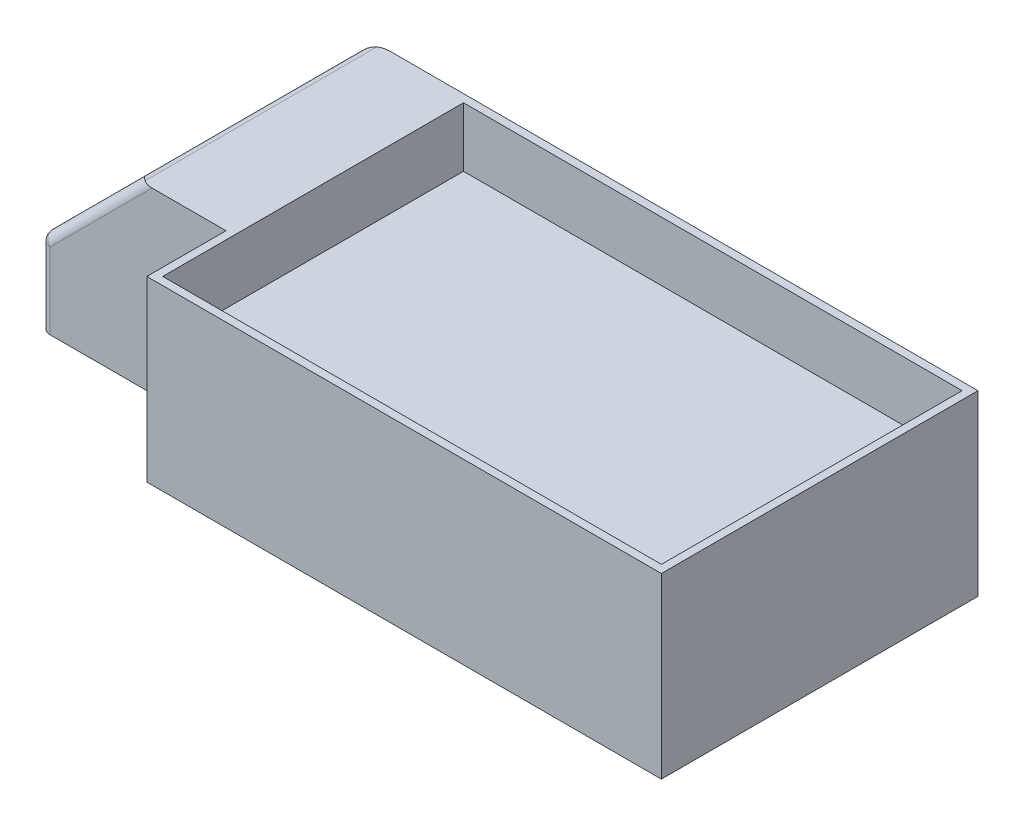
SolidWorks part; units mm, degrees
ref_plane "Front Plane" through (0, 0, 0) normal (0, 0, 1) x (1, 0, 0)
ref_plane "Top Plane" through (0, 0, 0) normal (0, 1, 0) x (1, 0, 0)
ref_plane "Right Plane" through (0, 0, 0) normal (1, 0, 0) x (0, 0, -1)
sketch "Sketch1" plane through (0, 0, 0) normal (0, 1, 0) x (1, 0, 0)
  line L1 (0, 0) -> (130, 0)
  line L2 (0, 0) -> (0, 80)
  line L3 (0, 80) -> (130, 80)
  line L4 (130, 0) -> (130, 80)
  dimension "D1" = 80
  dimension "D2" = 130
extrude "Boss-Extrude1" add sketch "Sketch1" along normal blind 45 contours L3 L4 L1 L2
sketch "Sketch3" plane through (0, 0, 0) normal (0, 0, 1) x (1, 0, 0)
  line L0 (0, 0) -> (0, 45)
  line L1 (-46.9514, 20.2513) -> (-46.9514, 0)
  line L2 (-46.9514, 0) -> (0, 0)
  line L3 (-46.9514, 20.2513) -> (-22.2027, 45)
  line L4 (-22.2027, 45) -> (0, 45)
  line L5 (0, 45) -> (0, 0) construction
  line L6 (0, 0) -> (130, 0) construction
  dimension "D1" = 35
extrude "Boss-Extrude3" add sketch "Sketch3" against normal up to surface (80 mm away) contours L3 L4 L0 L2 L1 up to face at (65, 22.5, -80)
extrude "Cut-Extrude1" cut sketch "Sketch3<4>" against normal blind 20
sketch "Sketch3<4>" plane through (0, 0, 0) normal (0, 0, 1) x (1, 0, 0) same geometry as "Sketch3"
fillet "Fillet2" radius 2.5 6 edges at (-46.9514, 20.2513, -50) (-34.5771, 32.6256, -80) (-22.2027, 45, -50) (-34.5771, 32.6256, -20) (-46.9514, 10.1256, -20) (-46.9514, 10.1256, -80)
shell "Shell2" thickness 4 removed face at (9.5198, 0, -37.5)
sketch "Sketch9" plane through (0, 45, 0) normal (0, 1, 0) x (1, 0, 0)
  line L0 (-18.6671, 80) -> (130, 80) construction
  line L1 (130, 0) -> (0, 0)
  line L2 (130, 0) -> (130, 80)
  line L3 (130, 80) -> (0, 80)
  line L4 (0, 0) -> (0, 80)
  line L5 (0, 0) -> (0, 80)
  line L6 (130, 80) -> (0, 80)
  line L7 (130, 0) -> (130, 80)
  line L8 (130, 0) -> (0, 0)
  line L9 (128, 2) -> (2, 2)
  line L10 (2, 2) -> (2, 78)
  line L11 (128, 78) -> (2, 78)
  line L12 (128, 2) -> (128, 78)
  line L13 (2, 2) -> (2, 78)
  line L14 (128, 78) -> (2, 78)
  line L15 (128, 2) -> (128, 78)
  line L16 (128, 2) -> (2, 2)
  dimension "D1" = 0
  dimension "D2" = 2
extrude "Boss-Extrude7" add sketch "Sketch9" against normal blind 20 contours L4 L3 L2 L1
extrude "Cut-Extrude3" cut sketch "Sketch9<3>" against normal blind 15 contours L9 L12 L11 L10 region at (65, 45, -40)
sketch "Sketch9<3>" plane through (0, 45, 0) normal (0, 1, 0) x (1, 0, 0) same geometry as "Sketch9"
sketch "Sketch10" plane through (-33.6013, 33.6013, 0) normal (-0.7071, 0.7071, 0) x (0, 0, 1)
  line L0 (-77.5, 15.0846) -> (-22.5, -17.8443) construction
  line L1 (-22.5, 15.0846) -> (-77.5, -17.8443) construction
  line L7 (-62.5, 6.1201) -> (-37.5, 6.1201)
  line L8 (-62.5, 6.1201) -> (-62.5, -8.8799)
  line L9 (-62.5, -8.8799) -> (-37.5, -8.8799)
  line L10 (-37.5, 6.1201) -> (-37.5, -8.8799)
  point P12 (-50, -1.3799)
  point P13 (-50, 6.1201)
  point P14 (-62.5, -1.3799)
  dimension "D1" = 25
  dimension "D2" = 15
extrude "Cut-Extrude4" cut sketch "Sketch10" against normal blind 15
